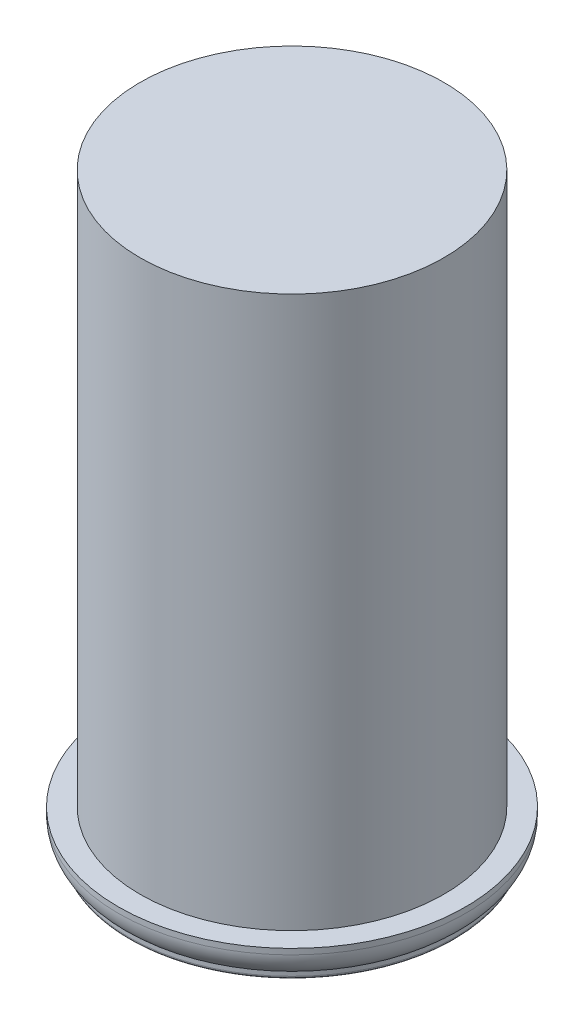
SolidWorks part; units mm, degrees
ref_plane "Front Plane" through (0, 0, 0) normal (0, 0, 1) x (1, 0, 0)
ref_plane "Top Plane" through (0, 0, 0) normal (0, 1, 0) x (1, 0, 0)
ref_plane "Right Plane" through (0, 0, 0) normal (1, 0, 0) x (0, 0, -1)
sketch "Sketch1" plane through (0, 0, 0) normal (0, 1, 0) x (1, 0, 0)
  circle A0 centre (0, 0) radius 16
  dimension "D1" = 32
extrude "Boss-Extrude1" add sketch "Sketch1" along normal blind 2.54
sketch "Sketch2" plane through (0, 2.54, 0) normal (0, 1, 0) x (1, 0, 0)
  circle A0 centre (0, 0) radius 14
  dimension "D1" = 28
extrude "Boss-Extrude2" add sketch "Sketch2" along normal blind 50.8
sketch "Sketch3" plane through (0, 0, 0) normal (0, -1, 0) x (1, 0, 0)
  circle A0 centre (0, 0) radius 15
  dimension "D1" = 30
extrude "Boss-Extrude3" add sketch "Sketch3" along normal blind 2.54
dome "Dome1" faces to dome 1 distance 12.7 reverse direction yes elliptical dome no face at (0, -2.54, -15) parameters "D1"=12.7
fillet "Fillet1" radius 2.54 1 edges at (0, 0, 16)
fillet "Fillet2" radius 0.254 1 edges at (0, -2.54, -15)
